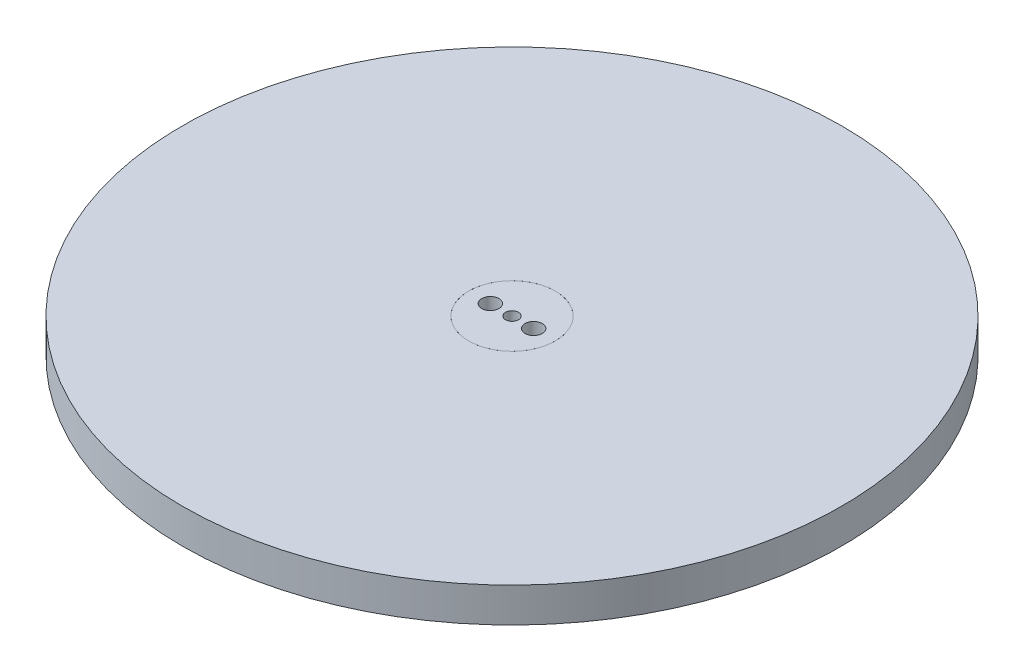
SolidWorks part; units mm, degrees
ref_plane "Front Plane" through (0, 0, 0) normal (0, 0, 1) x (1, 0, 0)
ref_plane "Top Plane" through (0, 0, 0) normal (0, 1, 0) x (1, 0, 0)
ref_plane "Right Plane" through (0, 0, 0) normal (1, 0, 0) x (0, 0, -1)
sketch "Sketch1" plane through (0, 0, 0) normal (0, 1, 0) x (1, 0, 0)
  line L0 (-2.5, 0) -> (2.5, 0) construction
  line L1 (0, 5) -> (0, -5) construction
  circle A1 centre (0, 0) radius 0.75
  circle A2 centre (-2.5, 0) radius 1
  circle A4 centre (0, 0) radius 5
  circle A5 centre (2.5, 0) radius 1
  dimension "D1" = 2.5
  dimension "D2" = 1.5
  dimension "D3" = 2
  dimension "D4" = 10
extrude "Boss-Extrude1" add sketch "Sketch1" along normal mid plane 4
sketch "Sketch2" plane through (0, -2, 0) normal (0, -1, 0) x (1, 0, 0)
  circle A0 centre (0, 0) radius 38.1
  circle A1 centre (0, 0) radius 5
  circle A2 centre (0, 0) radius 5
  dimension "D2" = 76.2
  dimension "D1" = 0
extrude "Boss-Extrude2" add sketch "Sketch2" against normal up to surface (4 mm away) separate body up to face at (-2.5, 2, 1)
